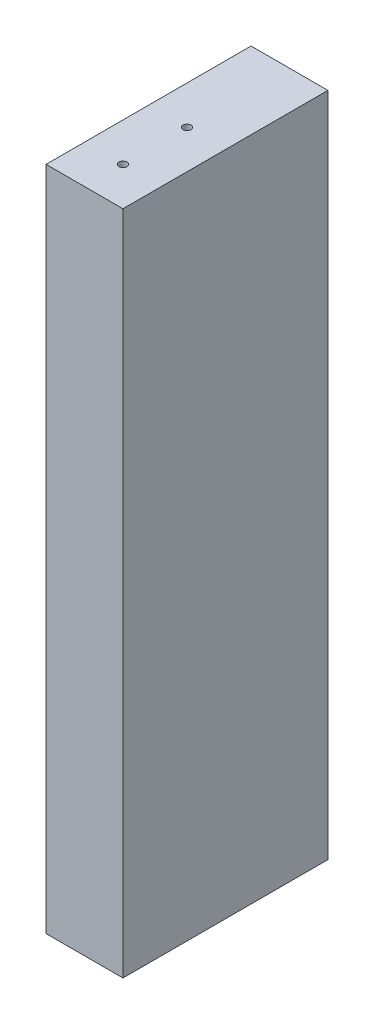
SolidWorks part; units mm, degrees
material "Beech"
ref_plane "Front" through (0, 0, 0) normal (0, 0, 1) x (1, 0, 0)
ref_plane "Top" through (0, 0, 0) normal (0, 1, 0) x (1, 0, 0)
ref_plane "Right" through (0, 0, 0) normal (1, 0, 0) x (0, 0, -1)
sketch "Sketch1" plane through (0, 0, 0) normal (0, 0, 1) x (1, 0, 0)
  line L0 (273.05, 6101.08) -> (475.4926, 6101.08) construction
  line L1 (450.0926, 6101.08) -> (431.0426, 6101.08)
  line L2 (450.0926, 6101.08) -> (450.0926, 6266.18)
  line L3 (450.0926, 6266.18) -> (431.0426, 6266.18)
  line L4 (431.0426, 6101.08) -> (431.0426, 6266.18)
  line L5 (481.7563, 6266.18) -> (273.05, 6266.18) construction
  dimension "D1" = 25.4
  dimension "D2" = 19.05
extrude "Boss-Extrude1" add sketch "Sketch1" along normal blind 50.8
hole_wizard "5/64 (0.07813) Diameter Hole1" positions "Sketch2" profile "Sketch3" hole size "5/64" standard "ANSI Inch"
sketch "Sketch2" plane through (4.969, 0, -19.0501) normal (0, 0, -1) x (-1, 0, 0)
  point P0 (-481.5892, 6993.255)
  point P9 (-386.3392, 6993.255)
  point P18 (-291.0892, 6993.255)
  point P21 (-295.275, 6965.1359)
  point P33 (-295.275, 6812.7359)
  point P45 (-295.275, 6660.3359)
  point P48 (-285.1664, 6631.4688)
  point P66 (-475.4773, 6631.4688)
  point P69 (-485.0023, 6660.3359)
  point P81 (-485.0023, 6812.7359)
  point P93 (-485.0023, 6965.1359)
  point P96 (-478.3656, 6611.6708)
  point P114 (-287.8656, 6611.6708)
  point P117 (-307.975, 6564.3379)
  point P127 (-307.975, 6488.1379)
  point P130 (-284.9609, 6440.805)
  point P143 (-380.2109, 6440.805)
  point P152 (-475.4609, 6440.805)
  point P155 (-446.8313, 6488.1379)
  point P161 (-446.8313, 6564.3379)
  point P164 (-472.2313, 6396.355)
  point P170 (-472.2313, 6320.155)
  point P173 (-472.6532, 6275.705)
  point P182 (-377.4032, 6275.705)
  point P191 (-282.1532, 6275.705)
  point P194 (-282.575, 6320.155)
  point P200 (-282.575, 6396.355)
  point P203 (-435.5986, 6221.73)
  point P209 (-435.5986, 6145.53)
  point P233 (-450.5925, 6091.555)
  point P242 (-460.9986, 6091.5555)
  point P245 (-460.9986, 6056.63)
  point P251 (-460.9986, 5980.43)
  point P263 (-460.9986, 5945.505)
  point P280 (-282.1532, 5945.505)
  point P284 (-368.6118, 5945.505)
sketch "Sketch3" plane through (486.5582, 6993.255, -19.0501) normal (1, 0, 0) x (0, 1, 0)
  line L0 (0, 0) -> (0, 38.6962)
  line L1 (0, 38.6962) -> (0.9923, 38.1)
  line L2 (0.9923, 38.1) -> (0.9923, 0)
  line L3 (0.9923, 0) -> (0, 0)
  line L4 (0, 38.6962) -> (-0.9923, 38.1) construction
  line L5 (0, -6.35) -> (0, 107.95) construction
  dimension "Hole Dia." = 1.9845
  dimension "Hole Depth" = 38.1
  dimension "Drill Angle" = 118
hole_wizard "5/64 (0.07813) Diameter Hole2" positions "Sketch4" profile "Sketch5" hole size "5/64" standard "ANSI Inch"
sketch "Sketch4" plane through (0, 6101.08, 0) normal (0, -1, 0) x (-1, 0, 0)
  line L0 (-440.5676, -50.8) -> (-440.5676, 0) construction
  line L1 (-431.0426, -50.8) -> (-450.0926, -50.8) construction
  line L2 (-480.4616, 0) -> (-278.019, 0.0001) construction
  point P0 (-440.5676, -41.275)
  point P2 (-440.5676, -25.4)
  dimension "D1" = 15.875
sketch "Sketch5" plane through (440.5676, 6101.08, 41.275) normal (1, 0, 0) x (0, 0, -1)
  line L0 (0, 0) -> (0, 19.6462)
  line L1 (0, 19.6462) -> (0.9923, 19.05)
  line L2 (0.9923, 19.05) -> (0.9923, 0)
  line L5 (0.9923, 0) -> (0, 0)
  line L10 (0, 19.6462) -> (-0.9923, 19.05) construction
  line L11 (0, -6.35) -> (0, 107.95) construction
  dimension "Hole Dia." = 1.9845
  dimension "Hole Depth" = 19.05
  dimension "Drill Angle" = 118
hole_wizard "5/64 (0.07813) Diameter Hole3" positions "Sketch6" profile "Sketch7" hole size "5/64" standard "ANSI Inch"
sketch "Sketch6" plane through (0, 6266.18, 0) normal (0, 1, 0) x (1, 0, 0)
  circle A0 centre (440.5676, -41.275) radius 0.9923 construction
  circle A1 centre (440.5676, -25.4) radius 0.9923 construction
  point P0 (440.5676, -25.4)
  point P2 (440.5676, -41.275)
sketch "Sketch7" plane through (440.5676, 6266.18, 25.4) normal (1, 0, 0) x (0, 0, 1)
  line L0 (0, 0) -> (0, 19.6462)
  line L1 (0, 19.6462) -> (0.9923, 19.05)
  line L2 (0.9923, 19.05) -> (0.9923, 0)
  line L5 (0.9923, 0) -> (0, 0)
  line L10 (0, 19.6462) -> (-0.9923, 19.05) construction
  line L11 (0, -6.35) -> (0, 107.95) construction
  dimension "Hole Dia." = 1.9845
  dimension "Hole Depth" = 19.05
  dimension "Drill Angle" = 118
